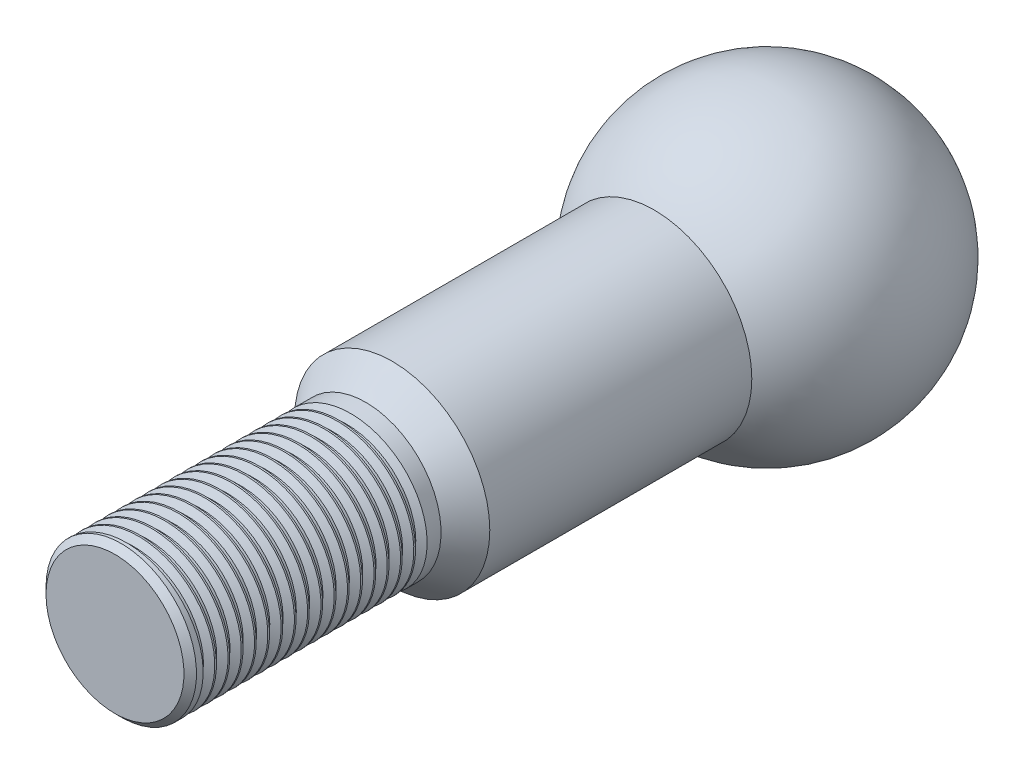
SolidWorks part; units mm, degrees
ref_plane "Front Plane" through (0, 0, 0) normal (0, 0, 1) x (1, 0, 0)
ref_plane "Top Plane" through (0, 0, 0) normal (0, 1, 0) x (1, 0, 0)
ref_plane "Right Plane" through (0, 0, 0) normal (1, 0, 0) x (0, 0, -1)
sketch "Sketch3" plane through (0, 0, 0) normal (0, 1, 0) x (1, 0, 0)
  line L0 (0, 0) -> (6, 0)
  line L1 (6, 0) -> (6, 20)
  line L2 (6, 20) -> (7.78, 20)
  line L3 (7.78, 20) -> (7.78, 43)
  line L4 (7.78, 43) -> (0, 43)
  line L5 (0, 43) -> (0, 0)
  line L6 (0, 43) -> (0, 52)
  line L7 (0, 52) -> (0, 63.8966)
  line L8 (6, 20) -> (7.78, 22.1077)
  arc A0 (0, 40.1034) -> (0, 63.8966) centre (0, 52) ccw
  dimension "D1" = 6
  dimension "D2" = 20
  dimension "D3" = 1.78
  dimension "D4" = 23
  dimension "D5" = 9
revolve "Revolve1" add sketch "Sketch3" angle 360 about L5 region at (3.5392, 0, -21.8451) region at (2.9715, 0, -41.8284) region at (5.204, 0, -52.7588)
sketch "Sketch8" plane through (0, 0, 0) normal (0, 1, 0) x (1, 0, 0)
  line L0 (0, 52) -> (0, -10.1642) construction
  arc A3 (7.78, 43) -> (-7.78, 43) centre (0, 52) ccw construction
  point P0 (0, 52)
  point P2 (0, 20.9179)
chamfer "Chamfer4" distance 0.5 angle 45 1 edges at (-6, 0, 0)
thread "Thread2" pitch 1.0583 method cut profile "Thread Profile2" start angle 0, offset 0, length 18, pitch 1.0583, diameter 12
ref_plane "Plane2" through (-6, 0, -0.5) normal (0, -1, 0) x (-1, 0, 0)
sketch "Thread Profile2" plane through (-6, 0, -0.5) normal (0, -1, 0) x (-1, 0, 0)
  line L0 (0, 0) -> (0, 1.0583) construction
  line L11 (0, 0) -> (0, 0.926)
  line L12 (0, 0.926) -> (-0.5728, 0.5953)
  line L13 (-0.5728, 0.5953) -> (-0.5728, 0.3307)
  line L15 (-0.5728, 0.3307) -> (0, 0)
  line L17 (-0.5728, 0.463) -> (0, 0.463) construction
  point P2 (0, 0)
  dimension "Pitch" = 1.0583
  dimension "Profile_Angle" = 60
  dimension "Profile_Land" = 0.2646
  dimension "Profile_Height" = 0.5728
